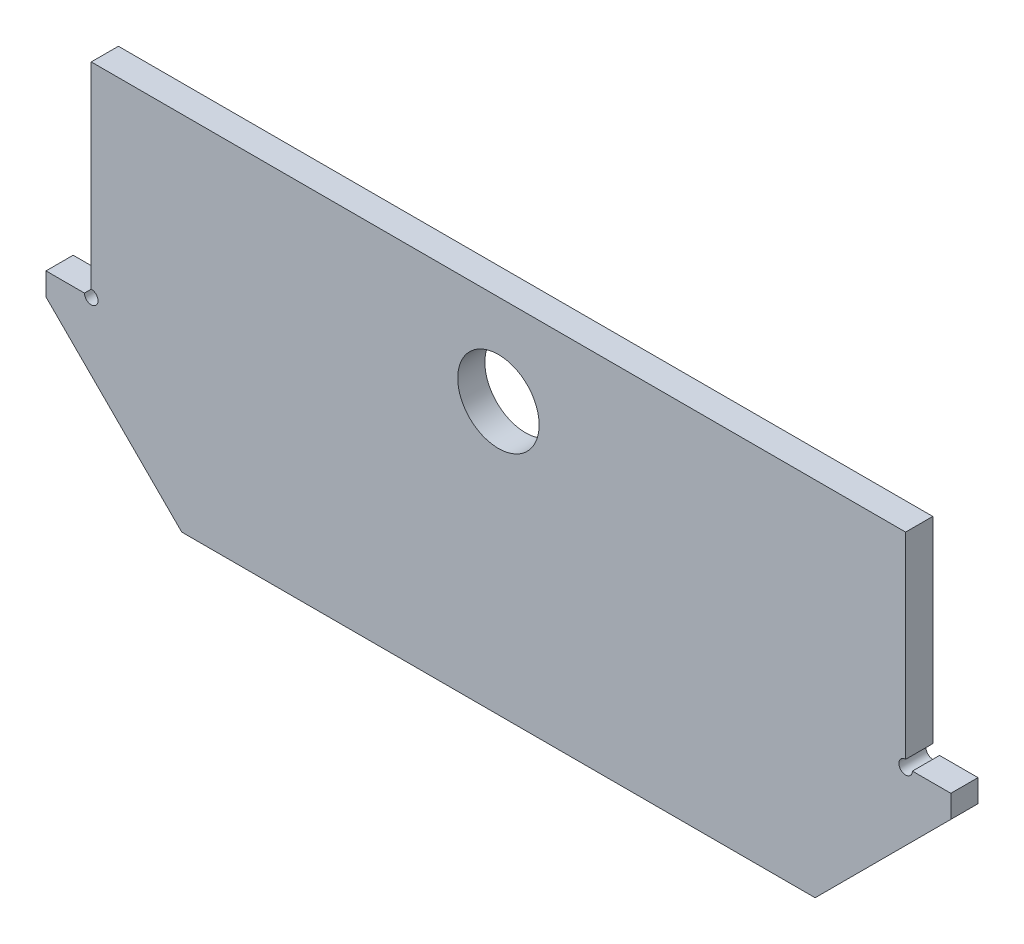
SolidWorks part; units mm, degrees
material "Plain Carbon Steel"
ref_plane "Front Plane" through (0, 0, 0) normal (0, 0, 1) x (1, 0, 0)
ref_plane "Top Plane" through (0, 0, 0) normal (0, 1, 0) x (1, 0, 0)
ref_plane "Right Plane" through (0, 0, 0) normal (1, 0, 0) x (0, 0, -1)
sketch "Sketch1" plane through (0, 0, 0) normal (0, 0, 1) x (1, 0, 0)
  line L0 (90, -1414) -> (90, -1294) construction
  line L2 (-90, -1414) -> (-90, -1369)
  line L3 (-90, -1369) -> (90, -1369)
  line L4 (90, -1414) -> (90, -1369)
  line L5 (671, -1414) -> (-671, -1414) construction
  line L6 (150, -1414) -> (150, -1294) construction
  line L7 (-100, -1414) -> (-90, -1414)
  line L8 (-100, -1414) -> (-100, -1419)
  line L9 (-70, -1449) -> (70, -1449)
  line L10 (100, -1414) -> (100, -1419)
  line L11 (90, -1414) -> (100, -1414)
  line L12 (-100, -1419) -> (-70, -1449)
  line L13 (70, -1449) -> (100, -1419)
  line L14 (-30.8239, -1354) -> (30.8239, -1354) construction
  line L15 (-90, -1409) -> (-90, -1299) construction
  point P10 (100, -1449)
  point P11 (-100, -1449)
  dimension "D1" = 80
  dimension "D2" = 15
  dimension "D3" = 200
extrude "Boss-Extrude1" add sketch "Sketch1" along normal blind 3 and the other way blind 3
sketch "Sketch2" plane through (0, 0, 3) normal (0, 0, 1) x (1, 0, 0)
  circle A1 centre (0, -1389) radius 9
  dimension "D1" = 18
extrude "Cut-Extrude1" cut sketch "Sketch2" against normal through all both and the other way through all
sketch "Sketch3" plane through (0, 0, 3) normal (0, 0, 1) x (1, 0, 0)
  circle A0 centre (-90, -1414) radius 1.5
  circle A1 centre (90, -1414) radius 1.5
  dimension "D1" = 3
  dimension "D2" = 3
extrude "Cut-Extrude2" cut sketch "Sketch3" against normal through all both and the other way through all
